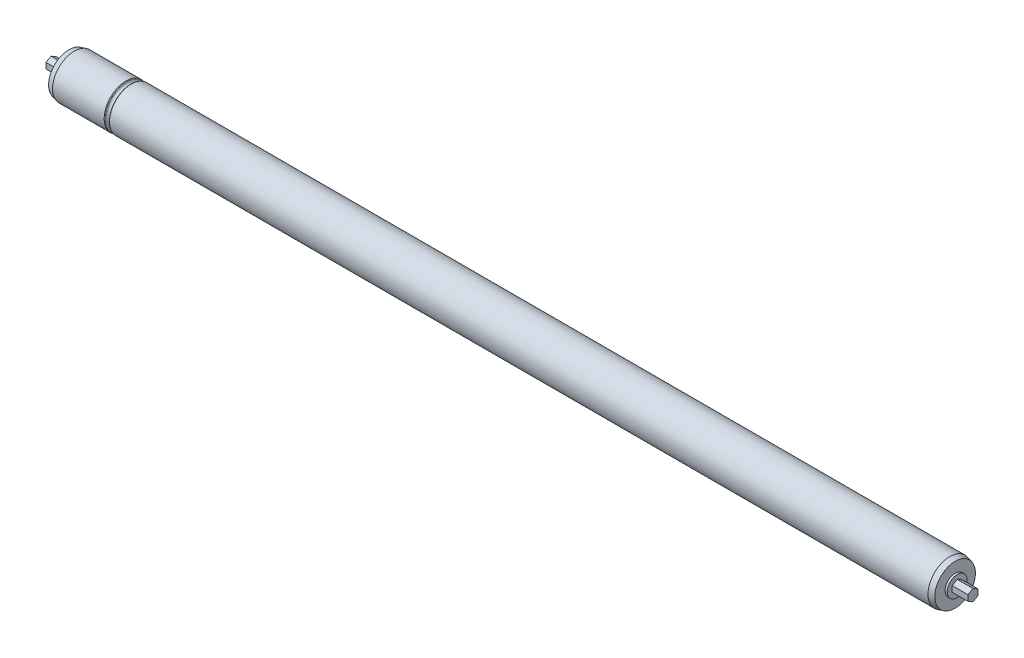
SolidWorks part; units mm, degrees
ref_plane "Front Plane" through (0, 0, 0) normal (0, 0, 1) x (1, 0, 0)
ref_plane "Top Plane" through (0, 0, 0) normal (0, 1, 0) x (1, 0, 0)
ref_plane "Right Plane" through (0, 0, 0) normal (1, 0, 0) x (0, 0, -1)
sketch "Sketch1" plane through (0, 0, 0) normal (0, 0, 1) x (1, 0, 0)
  line L0 (-493.7125, 0) -> (493.7125, 0) construction
  line L1 (493.7125, 0) -> (511.175, 0) construction
  line L2 (-493.7125, 0) -> (-511.175, 0) construction
  line L3 (0, 24.13) -> (0, -24.13) construction
  line L4 (-511.175, 5.5562) -> (-511.175, -5.5563) construction
  line L5 (511.175, 5.5562) -> (511.175, -5.5562) construction
  line L6 (-490.1406, 24.13) -> (-490.1406, -24.13) construction
  line L7 (-490.1406, 0) -> (490.1406, 0) construction
  line L8 (490.1406, 24.13) -> (490.1406, -24.13) construction
  line L9 (-425.1325, 24.13) -> (-425.1325, -24.13) construction
  line L10 (-427.5137, 20.9867) -> (-422.7512, 20.9867) construction
  line L11 (-495.3, 11.1125) -> (-495.3, -11.1125) construction
  line L12 (495.3, 11.1125) -> (495.3, -11.1125) construction
  point P2 (-495.3, 0)
  point P6 (495.3, 0)
  point P23 (-425.1325, 20.9867)
  dimension "D1" = 1.5875
  dimension "D2" = 1.5875
  dimension "BF" = 990.6
  dimension "D3" = 1022.35
  dimension "D4" = 48.26
  dimension "D5" = 11.1125
  dimension "D6" = 980.2812
  dimension "D8" = 3.1432
  dimension "D9" = 4.7625
  dimension "D10" = 22.225
  dimension "D7" = 68.58
sketch "Sketch2" plane through (0, 0, 0) normal (0, 0, 1) x (1, 0, 0)
  line L0 (-493.7125, 0) -> (-493.7125, 11.1125)
  line L1 (-493.7125, 11.1125) -> (-491.3313, 11.1125)
  line L2 (-491.3313, 11.1125) -> (-491.3313, 22.541)
  line L3 (-493.7125, 0) -> (-500.7221, 0) construction
  line L4 (-490.1406, 22.86) -> (-490.1406, 0)
  line L5 (-493.7125, 0) -> (-490.1406, 0) construction
  line L6 (-493.7125, 0) -> (-490.1406, 0)
  line L7 (-490.1406, 22.86) -> (-491.3313, 22.541)
  dimension "D1" = 3.5719
  dimension "D2" = 1.1906
  dimension "D3" = 22.225
  dimension "D4" = 45.72
  dimension "D5" = 15
revolve "Revolve1" add sketch "Sketch2" angle 360 mid plane about L5
mirror "Mirror2" about plane through (0, 0, 0) normal (1, 0, 0) of bodies 101
sketch "Sketch3" plane through (0, 0, 0) normal (1, 0, 0) x (0, 0, -1)
  circle A0 centre (0, 0) radius 24.13
extrude "Boss-Extrude1" add sketch "Sketch3" against normal up to vertex (490.1406 mm away) and the other way up to vertex (490.1406 mm away) separate body up to point (-490.1406, 0, 0) other way up to point (490.1406, 0, 0)
sketch "Sketch6" plane through (-491.3313, 0, 0) normal (-1, 0, 0) x (0, 0, 1)
  circle A0 centre (0, 0) radius 22.541 construction
  circle A1 centre (0, 0) radius 22.541
extrude "Cut-Extrude2" cut sketch "Sketch6" against normal through all draft 15 flip side to cut
sketch "Sketch7" plane through (491.3313, 0, 0) normal (1, 0, 0) x (0, 0, -1)
  circle A0 centre (0, 0) radius 22.541 construction
  circle A1 centre (0, 0) radius 22.541
extrude "Cut-Extrude3" cut sketch "Sketch7" against normal through all draft 15 flip side to cut
sketch "Sketch4" plane through (0, 0, 0) normal (1, 0, 0) x (0, 0, -1)
  line L1 (0, 6.4158) -> (-5.5563, 3.2079)
  line L2 (-5.5563, 3.2079) -> (-5.5563, -3.2079)
  line L3 (-5.5563, -3.2079) -> (0, -6.4158)
  line L4 (0, -6.4158) -> (5.5562, -3.2079)
  line L5 (5.5562, -3.2079) -> (5.5562, 3.2079)
  line L6 (5.5562, 3.2079) -> (0, 6.4158)
  circle A0 centre (0, 0) radius 5.5563 construction
  dimension "D1" = 11.1125
extrude "Boss-Extrude2" add sketch "Sketch4" along normal up to vertex and the other way up to vertex up to point (511.175, 0, 0) other way up to point (-511.175, 0, 0)
sketch "Sketch5" plane through (0, 0, 0) normal (0, 0, 1) x (1, 0, 0)
  line L0 (-427.5137, 20.9867) -> (-422.7512, 20.9867) construction
  line L1 (-425.1325, 24.13) -> (-425.1325, -24.13) construction
  line L2 (-427.5137, 20.9867) -> (-427.5137, 28.0831) construction
  line L3 (-511.175, 0) -> (-493.7125, 0) construction
  line L7 (-425.1325, 23.368) -> (-427.5137, 23.368) construction
  line L8 (-428.3011, 24.1554) -> (-428.3011, 24.7904)
  line L9 (-428.3011, 24.7904) -> (-421.9638, 24.7904)
  line L10 (-421.9638, 24.1554) -> (-421.9638, 24.7904)
  arc A0 (-427.5137, 23.368) -> (-422.7512, 23.368) centre (-425.1325, 23.368) ccw
  arc A1 (-422.7512, 23.368) -> (-421.9638, 24.1554) centre (-421.9638, 23.368) cw
  arc A2 (-427.5137, 23.368) -> (-428.3011, 24.1554) centre (-428.3011, 23.368) ccw
  dimension "D2" = 0.7874
  dimension "D1" = 0.762
  dimension "D3" = 0.635
revolve "Cut-Revolve1" cut sketch "Sketch5" angle 360 mid plane about L3
ref_axis "Center Axis 1" through (-408.6225, 0, 0) along (1, 0, 0)
ref_plane "Contact Plane 1" through (-511.175, 0, 0) normal (-1, 0, 0) x (0, 0, 1)
ref_plane "Contact Plane 2" through (-493.7125, 0, 0) normal (-1, 0, 0) x (0, 0, 1)
equation "\"D3@Sketch1\" = \"BF@Sketch1\"+1.25"
equation "\"D6@Sketch1\" = \"BF@Sketch1\"-.40625"
equation "\"D2@Sketch2\" = \"D1@Sketch2\"/3"
equation "\"D3@Sketch2\" = \"D5@Sketch1\"*2"
equation "\"D10@Sketch1\" = \"D3@Sketch2\""
